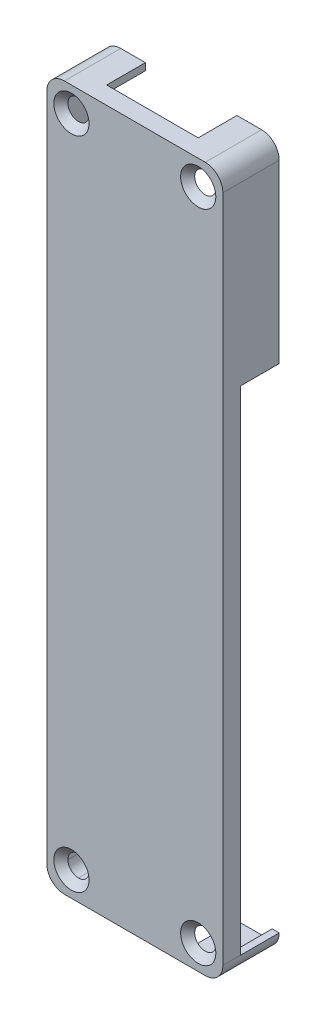
SolidWorks part; units mm, degrees
ref_plane "Piano frontale" through (0, 0, 0) normal (0, 0, 1) x (1, 0, 0)
ref_plane "Piano superiore" through (0, 0, 0) normal (0, 1, 0) x (1, 0, 0)
ref_plane "Piano destro" through (0, 0, 0) normal (1, 0, 0) x (0, 0, -1)
sketch "Schizzo1" plane through (0, 0, 0) normal (0, 0, 1) x (1, 0, 0)
  line L1 (-25, 100) -> (25, 100)
  line L2 (-25, 100) -> (-25, -100)
  line L3 (-25, -100) -> (25, -100)
  line L4 (25, 100) -> (25, -100)
  line L5 (-25, 100) -> (25, -100) construction
  line L6 (-25, -100) -> (25, 100) construction
  point P0 (0, 0)
  dimension "D1" = 50
  dimension "D2" = 200
extrude "Estrusione-Estrusione1" add sketch "Schizzo1" along normal blind 16
fillet "Raccordo1" radius 5 4 edges at (-25, -100, 8) (25, -100, 8) (-25, 100, 8) (25, 100, 8)
shell "Svuota1" thickness 2 removed face at (0, 0, 0)
sketch "Schizzo4" plane through (0, 100, 0) normal (0, 1, 0) x (1, 0, 0)
  line L0 (-13, 0) -> (-13, -11)
  line L1 (20, 0) -> (-20, 0) construction
  line L2 (-13, -11) -> (13, -11)
  line L3 (13, -11) -> (13, 0)
  point P5 (0, -11)
  dimension "D1" = 26
  dimension "D2" = 11
extrude "Taglio-Estrusione1" cut sketch "Schizzo4" against normal through all and the other way through all
sketch "Schizzo5" plane through (25, 0, 0) normal (1, 0, 0) x (0, 0, -1)
  line L0 (0, 45) -> (-11, 45)
  line L1 (0, -95) -> (0, 95) construction
  line L2 (-11, 45) -> (-11, -95)
  line L3 (-16, -95) -> (0, -95) construction
  line L4 (-11, -95) -> (0, -95)
  line L5 (0, -95) -> (0, 45)
  dimension "D1" = 140
  dimension "D2" = 11
sketch "Schizzo8" plane through (0, 0, 16) normal (0, 0, 1) x (1, 0, 0)
  line L0 (20, 100) -> (-20, 100) construction
  line L1 (-25, 95) -> (-25, -95) construction
  line L2 (25, -95) -> (25, 95) construction
  circle A0 centre (-18, 93) radius 3
  circle A1 centre (18, 93) radius 3
  dimension "D3" = 6
  dimension "D4" = 6
  dimension "D5" = 7
  dimension "D6" = 7
  dimension "D7" = 7
  dimension "D8" = 7
extrude "Taglio-Estrusione2" cut sketch "Schizzo8" against normal through all
mirror "Specchia1" about plane through (0, 0, 0) normal (0, 1, 0) of "Taglio-Estrusione2"
extrude "Taglio-Estrusione3" cut sketch "Schizzo5" against normal blind 7
chamfer "Smusso1" distance 2 angle 45 4 edges at (-15, -93, 16) (21, -93, 16) (-15, 93, 16) (21, 93, 16)
